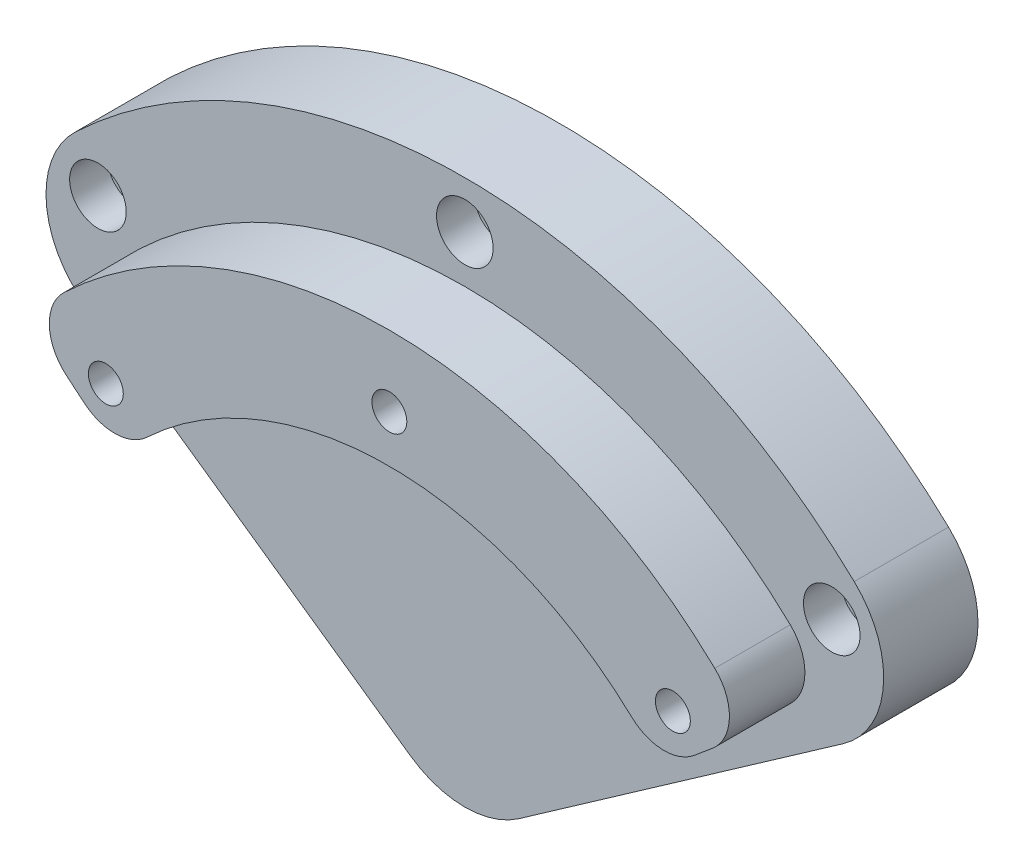
SolidWorks part; units mm, degrees
ref_plane "前视基准面" through (0, 0, 0) normal (0, 0, 1) x (1, 0, 0)
ref_plane "上视基准面" through (0, 0, 0) normal (0, 1, 0) x (1, 0, 0)
ref_plane "右视基准面" through (0, 0, 0) normal (1, 0, 0) x (0, 0, -1)
other "Configuration Table"
sketch "草图1" plane through (0, 0, 0) normal (0, 0, 1) x (1, 0, 0)
  line L0 (0, 60) -> (0, -60) construction
  line L1 (0, 0) -> (-49.1491, 34.4146)
  line L2 (0, 0) -> (49.1491, 34.4146)
  circle A0 centre (0, 0) radius 60
  dimension "D1" = 120
  dimension "D2" = 55
  dimension "D3" = 55
extrude "凸台-拉伸1" add sketch "草图1" along normal blind 10 contours A0 L0 L2 | L0 A0 L1 region at (17.7689, 34.1338, 0) region at (-17.7689, 34.1338, 0)
fillet "圆角1" radius 10 3 edges at (49.1491, 34.4146, 5) (-49.1491, 34.4146, 5) (0, 0, 5)
sketch "草图2" plane through (0, 0, 10) normal (0, 0, 1) x (1, 0, 0)
  line L2 (5.7358, 4.0162) -> (40.1301, 28.0994)
  line L3 (-40.1301, 28.0994) -> (-5.7358, 4.0162)
  line L4 (5.7358, 4.0162) -> (40.1301, 28.0994)
  line L5 (-40.1301, 28.0994) -> (-5.7358, 4.0162)
  circle A0 centre (0, 0) radius 55
  circle A1 centre (0, 55) radius 1.6
  circle A2 centre (38.8909, 38.8909) radius 1.6
  circle A3 centre (55, 0) radius 1.6
  arc A4 (40.1301, 28.0994) -> (41.2732, 43.5491) centre (34.3943, 36.2909) ccw
  arc A5 (41.2732, 43.5491) -> (-41.2732, 43.5491) centre (0, 0) ccw
  arc A6 (-41.2732, 43.5491) -> (-40.1301, 28.0994) centre (-34.3943, 36.2909) ccw
  arc A7 (-5.7358, 4.0162) -> (5.7358, 4.0162) centre (0, 12.2077) ccw
  arc A8 (40.1301, 28.0994) -> (41.2732, 43.5491) centre (34.3943, 36.2909) ccw
  arc A9 (41.2732, 43.5491) -> (-41.2732, 43.5491) centre (0, 0) ccw
  arc A10 (-41.2732, 43.5491) -> (-40.1301, 28.0994) centre (-34.3943, 36.2909) ccw
  arc A11 (-5.7358, 4.0162) -> (5.7358, 4.0162) centre (0, 12.2077) ccw
  circle A12 centre (38.8909, -38.8909) radius 1.6
  circle A13 centre (0, -55) radius 1.6
  circle A14 centre (-38.8909, -38.8909) radius 1.6
  circle A15 centre (-55, 0) radius 1.6
  circle A16 centre (-38.8909, 38.8909) radius 1.6
  point P29 (0, 0)
  dimension "D2" = 110
  dimension "D3" = 3.2
  dimension "D1" = 0
  dimension "D4" = 8
extrude "切除-拉伸1" cut sketch "草图2" against normal blind 10 contours A0 A16 | A0 A16 | A0 A1 | A0 A1 | A0 A2 | A0 A2 region at (38.4078, 38.4078, 10) region at (39.3681, 39.3681, 10) region at (-39.3681, 39.3681, 10) region at (-38.4078, 38.4078, 10) region at (0, 54.3168, 10) region at (0, 55.6749, 10)
sketch "草图3" plane through (0, 0, 10) normal (0, 0, 1) x (1, 0, 0)
  line L0 (0, 0) -> (38.3022, 32.1394)
  line L1 (0, 0) -> (-38.3022, 32.1394)
  line L2 (5.7358, 4.0162) -> (40.1301, 28.0994)
  line L3 (-40.1301, 28.0994) -> (-5.7358, 4.0162)
  line L4 (5.7358, 4.0162) -> (40.1301, 28.0994)
  line L5 (-40.1301, 28.0994) -> (-5.7358, 4.0162)
  line L6 (0, 50) -> (0, 0) construction
  circle A0 centre (0, 0) radius 37.5
  circle A1 centre (0, 0) radius 50
  circle A2 centre (0, 0) radius 42.5
  circle A3 centre (0, 42.5) radius 1.85
  arc A4 (40.1301, 28.0994) -> (41.2732, 43.5491) centre (34.3943, 36.2909) ccw
  arc A5 (41.2732, 43.5491) -> (-41.2732, 43.5491) centre (0, 0) ccw
  arc A6 (-41.2732, 43.5491) -> (-40.1301, 28.0994) centre (-34.3943, 36.2909) ccw
  arc A7 (-5.7358, 4.0162) -> (5.7358, 4.0162) centre (0, 12.2077) ccw
  arc A8 (40.1301, 28.0994) -> (41.2732, 43.5491) centre (34.3943, 36.2909) ccw
  arc A9 (41.2732, 43.5491) -> (-41.2732, 43.5491) centre (0, 0) ccw
  arc A10 (-41.2732, 43.5491) -> (-40.1301, 28.0994) centre (-34.3943, 36.2909) ccw
  arc A11 (-5.7358, 4.0162) -> (5.7358, 4.0162) centre (0, 12.2077) ccw
  circle A12 centre (30.052, 30.052) radius 1.85
  circle A13 centre (42.5, 0) radius 1.85
  circle A14 centre (30.052, -30.052) radius 1.85
  circle A15 centre (0, -42.5) radius 1.85
  circle A16 centre (-30.052, -30.052) radius 1.85
  circle A17 centre (-42.5, 0) radius 1.85
  circle A18 centre (-30.052, 30.052) radius 1.85
  point P32 (0, 0)
  dimension "D2" = 75
  dimension "D3" = 100
  dimension "D4" = 85
  dimension "D5" = 3.7
  dimension "D7" = 50
  dimension "D8" = 50
  dimension "D1" = 0
  dimension "D6" = 8
extrude "凸台-拉伸2" add sketch "草图3" along normal blind 8 contours A3 L6 A0 L0 A2 A12 | A1 L6 A3 A2 A12 L0 | L6 A1 L1 A2 A18 A3 | L6 A3 A2 A18 L1 A0 region at (16.2256, 35.2351, 10) region at (-16.2256, 35.2351, 10) region at (18.9265, 40.8502, 10) region at (-18.9265, 40.8502, 10)
fillet "圆角2" radius 5 4 edges at (-38.3022, 32.1394, 14) (-28.7267, 24.1045, 14) (28.7267, 24.1045, 14) (38.3022, 32.1394, 14)
sketch "草图4" plane through (0, 0, 18) normal (0, 0, 1) x (1, 0, 0)
  line L2 (32.3308, 27.1288) -> (34.2585, 28.7463)
  line L3 (-34.2585, 28.7463) -> (-32.3308, 27.1288)
  line L4 (32.3308, 27.1288) -> (34.2585, 28.7463)
  line L5 (-34.2585, 28.7463) -> (-32.3308, 27.1288)
  circle A0 centre (30.052, 30.052) radius 1.85 construction
  circle A1 centre (0, 42.5) radius 1.85 construction
  circle A2 centre (-30.052, 30.052) radius 1.85 construction
  circle A3 centre (30.052, 30.052) radius 1.85
  circle A4 centre (0, 42.5) radius 1.85
  circle A5 centre (-30.052, 30.052) radius 1.85
  arc A6 (25.6913, 27.3167) -> (-25.6913, 27.3167) centre (0, 0) ccw
  arc A7 (25.6913, 27.3167) -> (32.3308, 27.1288) centre (29.1169, 30.959) ccw
  arc A8 (34.2585, 28.7463) -> (34.494, 36.1962) centre (31.0446, 32.5766) ccw
  arc A9 (34.494, 36.1962) -> (-34.494, 36.1962) centre (0, 0) ccw
  arc A10 (-34.494, 36.1962) -> (-34.2585, 28.7463) centre (-31.0446, 32.5766) ccw
  arc A11 (-32.3308, 27.1288) -> (-25.6913, 27.3167) centre (-29.1169, 30.959) ccw
  arc A12 (25.6913, 27.3167) -> (-25.6913, 27.3167) centre (0, 0) ccw
  arc A13 (25.6913, 27.3167) -> (32.3308, 27.1288) centre (29.1169, 30.959) ccw
  arc A14 (34.2585, 28.7463) -> (34.494, 36.1962) centre (31.0446, 32.5766) ccw
  arc A15 (34.494, 36.1962) -> (-34.494, 36.1962) centre (0, 0) ccw
  arc A16 (-34.494, 36.1962) -> (-34.2585, 28.7463) centre (-31.0446, 32.5766) ccw
  arc A17 (-32.3308, 27.1288) -> (-25.6913, 27.3167) centre (-29.1169, 30.959) ccw
  circle M19 centre (30.052, 30.052) radius 1.85
  circle M20 centre (0, 42.5) radius 1.85
  dimension "D1" = 0
extrude "切除-拉伸2" cut sketch "草图4" against normal through all contours M20 | M19 | A5 region at (30.052, 30.052, 18) region at (0, 42.5, 18)
sketch "草图5" plane through (0, 0, 0) normal (0, 0, -1) x (-1, 0, 0)
  line L2 (-40.1301, 28.0994) -> (-5.7358, 4.0162)
  line L3 (5.7358, 4.0162) -> (40.1301, 28.0994)
  line L4 (-40.1301, 28.0994) -> (-5.7358, 4.0162)
  line L5 (5.7358, 4.0162) -> (40.1301, 28.0994)
  circle A0 centre (-30.052, 30.052) radius 1.85 construction
  circle A1 centre (30.052, 30.052) radius 1.85 construction
  circle A2 centre (0, 42.5) radius 1.85 construction
  circle A3 centre (-30.052, 30.052) radius 1.85
  arc A4 (41.2732, 43.5491) -> (-41.2732, 43.5491) centre (0, 0) ccw
  arc A5 (-41.2732, 43.5491) -> (-40.1301, 28.0994) centre (-34.3943, 36.2909) ccw
  arc A6 (-5.7358, 4.0162) -> (5.7358, 4.0162) centre (0, 12.2077) ccw
  arc A7 (40.1301, 28.0994) -> (41.2732, 43.5491) centre (34.3943, 36.2909) ccw
  arc A8 (41.2732, 43.5491) -> (-41.2732, 43.5491) centre (0, 0) ccw
  arc A9 (-41.2732, 43.5491) -> (-40.1301, 28.0994) centre (-34.3943, 36.2909) ccw
  arc A10 (-5.7358, 4.0162) -> (5.7358, 4.0162) centre (0, 12.2077) ccw
  arc A11 (40.1301, 28.0994) -> (41.2732, 43.5491) centre (34.3943, 36.2909) ccw
  circle A12 centre (30.052, 30.052) radius 1.85
  circle A13 centre (0, 42.5) radius 1.85
  circle A14 centre (-30.052, 30.052) radius 3.25
  circle A15 centre (0, 42.5) radius 3.25
  circle A16 centre (30.052, 30.052) radius 3.25
  circle M17 centre (-30.052, 30.052) radius 1.85
  circle M18 centre (0, 42.5) radius 1.85
  dimension "D2" = 6.5
  dimension "D3" = 6.5
  dimension "D4" = 6.5
  dimension "D1" = 0
extrude "切除-拉伸3" cut sketch "草图5" against normal blind 5 contours A14 M17 | A15 M18 | A12 | A16 region at (33.2101, 30.052, 0) region at (3.1581, 42.5, 0)
sketch "草图7" plane through (0, 0, 10) normal (0, 0, 1) x (1, 0, 0)
  line L2 (-34.2585, 28.7463) -> (-32.3308, 27.1288)
  line L3 (32.3308, 27.1288) -> (34.2585, 28.7463)
  line L4 (-34.2585, 28.7463) -> (-32.3308, 27.1288)
  line L5 (32.3308, 27.1288) -> (34.2585, 28.7463)
  circle A0 centre (-38.8909, 38.8909) radius 3
  circle A1 centre (38.8909, 38.8909) radius 1.6
  circle A2 centre (38.8909, 38.8909) radius 1.6
  circle A3 centre (0, 55) radius 1.6
  circle A4 centre (0, 55) radius 1.6
  circle A5 centre (-38.8909, 38.8909) radius 1.6
  circle A6 centre (-38.8909, 38.8909) radius 1.6
  circle A7 centre (0, 55) radius 3
  circle A8 centre (38.8909, 38.8909) radius 3
  arc A12 (25.6913, 27.3167) -> (-25.6913, 27.3167) centre (0, 0) ccw
  arc A13 (-32.3308, 27.1288) -> (-25.6913, 27.3167) centre (-29.1169, 30.959) ccw
  arc A14 (-34.494, 36.1962) -> (-34.2585, 28.7463) centre (-31.0446, 32.5766) ccw
  arc A15 (34.494, 36.1962) -> (-34.494, 36.1962) centre (0, 0) ccw
  arc A16 (34.2585, 28.7463) -> (34.494, 36.1962) centre (31.0446, 32.5766) ccw
  arc A17 (25.6913, 27.3167) -> (32.3308, 27.1288) centre (29.1169, 30.959) ccw
  arc A18 (25.6913, 27.3167) -> (-25.6913, 27.3167) centre (0, 0) ccw
  arc A19 (-32.3308, 27.1288) -> (-25.6913, 27.3167) centre (-29.1169, 30.959) ccw
  arc A20 (-34.494, 36.1962) -> (-34.2585, 28.7463) centre (-31.0446, 32.5766) ccw
  arc A21 (34.494, 36.1962) -> (-34.494, 36.1962) centre (0, 0) ccw
  arc A22 (34.2585, 28.7463) -> (34.494, 36.1962) centre (31.0446, 32.5766) ccw
  arc A23 (25.6913, 27.3167) -> (32.3308, 27.1288) centre (29.1169, 30.959) ccw
  dimension "D5" = 6
  dimension "D6" = 6
  dimension "D7" = 6
  dimension "D1" = 0
  dimension "D2" = 0
  dimension "D3" = 0
  dimension "D4" = 0
extrude "切除-拉伸5" cut sketch "草图7" against normal blind 4 contours A0 | A7 | A8
